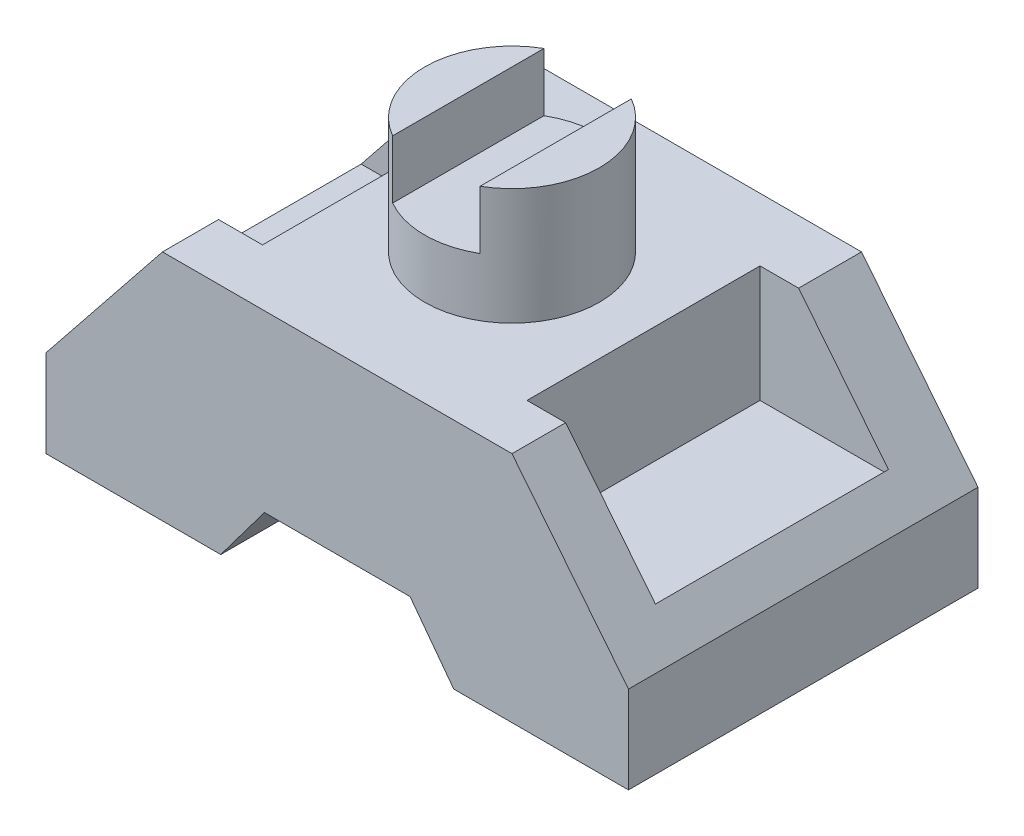
SolidWorks part; units mm, degrees
ref_plane "Plano frontal" through (0, 0, 0) normal (0, 0, 1) x (1, 0, 0)
ref_plane "Plano superior" through (0, 0, 0) normal (0, 1, 0) x (1, 0, 0)
ref_plane "Plano direito" through (0, 0, 0) normal (1, 0, 0) x (0, 0, -1)
sketch "Esboço1" plane through (0, 0, 0) normal (0, 0, 1) x (1, 0, 0)
  line L23 (0, 0) -> (0, 15)
  line L24 (0, 15) -> (20, 40)
  line L31 (37.5, 10) -> (30, 0)
  line L32 (30, 0) -> (0, 0)
  line L33 (20, 40) -> (80, 40)
  line L34 (50, 40) -> (50, 10)
  line L35 (62.5, 10) -> (37.5, 10)
  line L36 (70, 0) -> (100, 0)
  line L37 (62.5, 10) -> (70, 0)
  line L38 (100, 15) -> (80, 40)
  line L39 (100, 0) -> (100, 15)
  dimension "D1" = 20
  dimension "D2" = 12.5
  dimension "D3" = 40
  dimension "D4" = 15
  dimension "D5" = 30
  dimension "D6" = 50
extrude "Ressalto-extrusão2" add sketch "Esboço1" along normal blind 60 contours L35 L31 L32 L23 L24 L33 L38 L39 L36 L37
sketch "Esboço2" plane through (0, 40, 0) normal (0, 1, 0) x (1, 0, 0)
  circle A0 centre (50, -30) radius 15
  point P2 (0, 0)
  point P3 (50, -30)
  dimension "D1" = 30
extrude "Ressalto-extrusão4" add sketch "Esboço2" along normal blind 20
sketch "Esboço6" plane through (0, 60, 0) normal (0, 1, 0) x (1, 0, 0)
  line L1 (42.5, -5.7068) -> (57.5, -5.7068)
  line L2 (42.5, -5.7068) -> (42.5, -54.2932)
  line L3 (42.5, -54.2932) -> (57.5, -54.2932)
  line L4 (57.5, -5.7068) -> (57.5, -54.2932)
  line L5 (42.5, -5.7068) -> (57.5, -54.2932) construction
  line L6 (42.5, -54.2932) -> (57.5, -5.7068) construction
  point P0 (50, -30)
  dimension "D1" = 15
extrude "Corte-extrusão11" cut sketch "Esboço6" against normal blind 10
sketch "Esboço8" plane through (0, 40, 0) normal (0, 1, 0) x (1, 0, 0)
  line L1 (27.5518, -9.893) -> (-10.3743, -9.893)
  line L2 (27.5518, -9.893) -> (27.5518, -50.3817)
  line L3 (27.5518, -50.3817) -> (-10.3743, -50.3817)
  line L4 (-10.3743, -9.893) -> (-10.3743, -50.3817)
extrude "Corte-extrusão13" cut sketch "Esboço8" against normal blind 20
sketch "Esboço9" plane through (0, 40, 0) normal (0, 1, 0) x (1, 0, 0)
  line L1 (73.3707, -10.7917) -> (95.4089, -10.7917)
  line L2 (73.3707, -10.7917) -> (73.3707, -50.7917)
  line L3 (73.3707, -50.7917) -> (95.4089, -50.7917)
  line L4 (95.4089, -10.7917) -> (95.4089, -50.7917)
  point P4 (0, 0)
  dimension "D1" = 40
extrude "Corte-extrusão14" cut sketch "Esboço9" against normal blind 20 contours L2 L1 L4 L3
